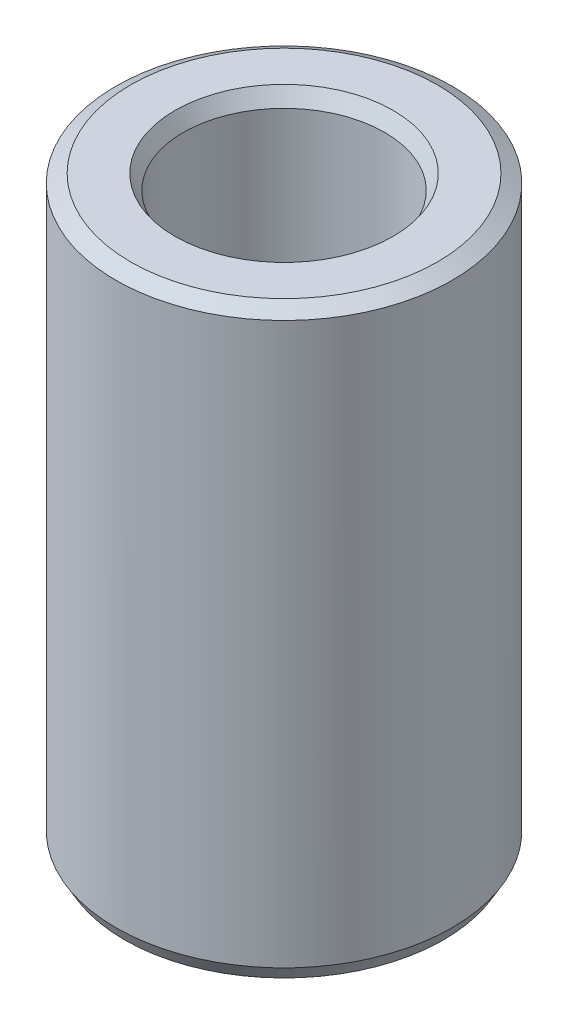
SolidWorks part; units mm, degrees
ref_plane "Front Plane" through (0, 0, 0) normal (0, 0, 1) x (1, 0, 0)
ref_plane "Top Plane" through (0, 0, 0) normal (0, 1, 0) x (1, 0, 0)
ref_plane "Right Plane" through (0, 0, 0) normal (1, 0, 0) x (0, 0, -1)
sketch "Sketch1" plane through (0, 0, 0) normal (0, 1, 0) x (1, 0, 0)
  circle A0 centre (0, 0) radius 52.5
  dimension "SLEEVE_OD" = 105
extrude "Boss-Extrude1" add sketch "Sketch1" along normal blind 182.3164
sketch "Sketch2" plane through (0, 0, 0) normal (0, 1, 0) x (1, 0, 0)
  circle A0 centre (0, 0) radius 31.4081
  dimension "BORE_D" = 62.8163
extrude "Cut-Extrude1" cut sketch "Sketch2" along normal through all
chamfer "Chamfer1" distance 2.6596 angle 60 4 edges at (0, 182.3164, 31.4081) (0, 0, 31.4081) (0, 0, 52.5) (0, 182.3164, 52.5) first distance on face at (0, 182.3164, 31.4081) first distance on face at (0, 0, 31.4081) first distance on face at (0, 182.3164, 52.5)
